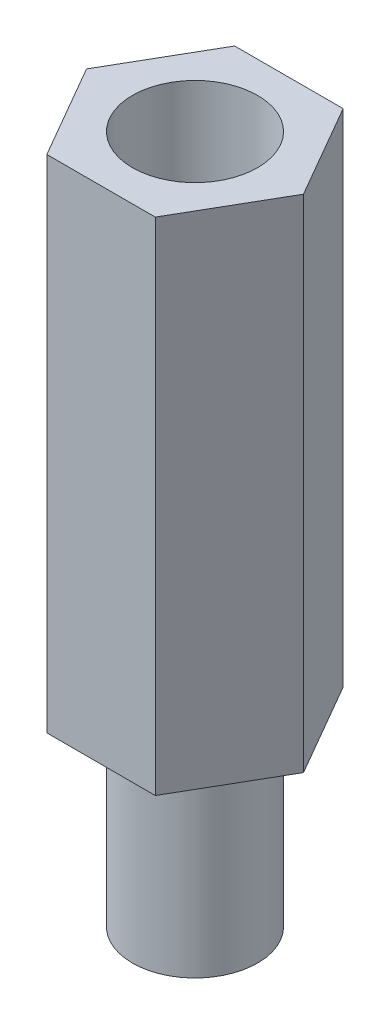
SolidWorks part; units mm, degrees
material "铜"
ref_plane "前视基准面" through (0, 0, 0) normal (0, 0, 1) x (1, 0, 0)
ref_plane "上视基准面" through (0, 0, 0) normal (0, 1, 0) x (1, 0, 0)
ref_plane "右视基准面" through (0, 0, 0) normal (1, 0, 0) x (0, 0, -1)
sketch "草图2" plane through (0, 0, 0) normal (0, 1, 0) x (1, 0, 0)
  line L1 (3.4641, 0) -> (1.7321, 3)
  line L2 (1.7321, 3) -> (-1.7321, 3)
  line L3 (-1.7321, 3) -> (-3.4641, 0)
  line L4 (-3.4641, 0) -> (-1.7321, -3)
  line L5 (-1.7321, -3) -> (1.7321, -3)
  line L6 (1.7321, -3) -> (3.4641, 0)
  circle A0 centre (0, 0) radius 3 construction
  circle A1 centre (0, 0) radius 2
  dimension "D2" = 4
  dimension "D1" = 6
extrude "凸台-拉伸1" add sketch "草图2" along normal blind 16
extrude "凸台-拉伸2" add sketch "草图2<2>" against normal blind 6 separate body contours A1 region at (0, 0, 0)
sketch "草图2<2>" plane through (0, 0, 0) normal (0, 1, 0) x (1, 0, 0) same geometry as "草图2"
